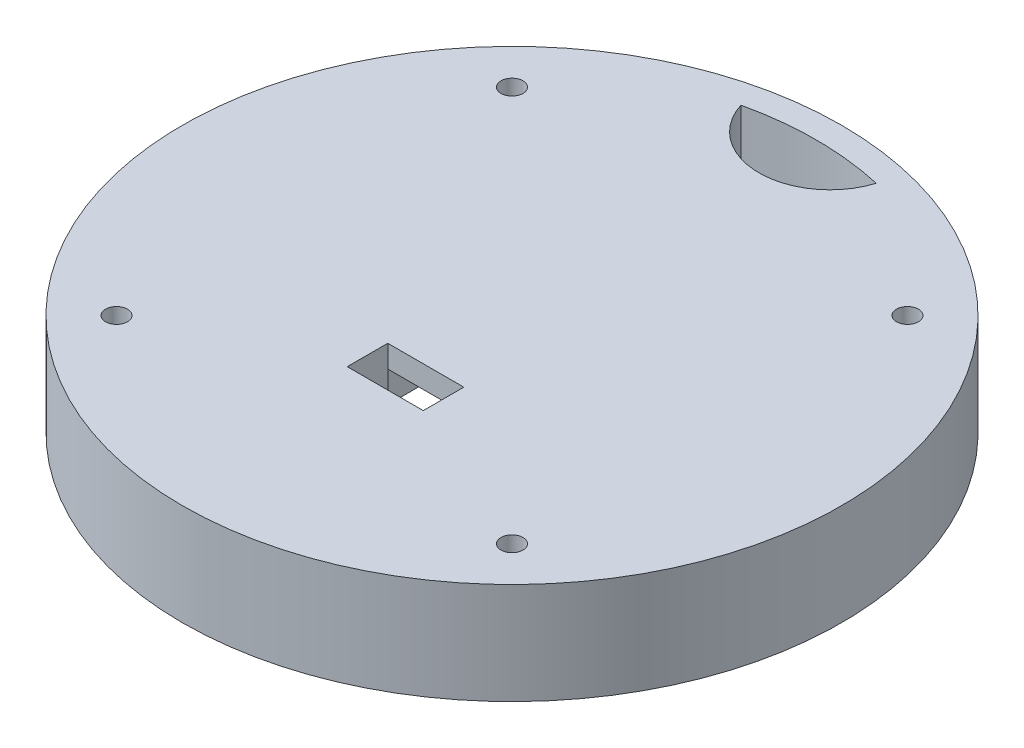
SolidWorks part; units mm, degrees
ref_plane "Front Plane" through (0, 0, 0) normal (0, 0, 1) x (1, 0, 0)
ref_plane "Top Plane" through (0, 0, 0) normal (0, 1, 0) x (1, 0, 0)
ref_plane "Right Plane" through (0, 0, 0) normal (1, 0, 0) x (0, 0, -1)
sketch "Sketch1" plane through (0, 0, 0) normal (0, 1, 0) x (1, 0, 0)
  line L1 (57.15, 57.15) -> (-57.15, 57.15) construction
  line L2 (57.15, 57.15) -> (57.15, -57.15) construction
  line L3 (57.15, -57.15) -> (-57.15, -57.15) construction
  line L4 (-57.15, 57.15) -> (-57.15, -57.15) construction
  line L5 (57.15, 57.15) -> (-57.15, -57.15) construction
  line L6 (57.15, -57.15) -> (-57.15, 57.15) construction
  line L7 (21.59, 21.59) -> (-21.59, 21.59)
  line L8 (21.59, 21.59) -> (21.59, -21.59)
  line L9 (21.59, -21.59) -> (-21.59, -21.59)
  line L10 (-21.59, 21.59) -> (-21.59, -21.59)
  line L11 (21.59, 21.59) -> (-21.59, -21.59) construction
  line L12 (21.59, -21.59) -> (-21.59, 21.59) construction
  circle A0 centre (-49.53, 49.53) radius 2.75
  circle A1 centre (49.53, 49.53) radius 2.75
  circle A2 centre (49.53, -49.53) radius 2.75
  circle A3 centre (-49.53, -49.53) radius 2.75
  circle A4 centre (0, 0) radius 82.55
  arc A6 (-16.9561, 74.2895) -> (16.9561, 74.2895) centre (0, 79.6392) ccw
  circle A7 centre (0, 0) radius 76.2
  point P0 (0, 0)
  point P14 (0, 0)
  point P25 (0, 0)
  dimension "D4" = 5.5
  dimension "D6" = 165.1
  dimension "D7" = 17.78
  dimension "D10" = 152.4
  dimension "D1" = 99.06
  dimension "D2" = 99.06
  dimension "D3" = 114.3
  dimension "D5" = 43.18
  dimension "D8" = 25.714
extrude "Boss-Extrude3" add sketch "Sketch1" along normal blind 25.4 contours A7 | A4 A7 | A7 A3 A2 A1 A0 L10 L7 L8 L9 | L7 L10 L9 L8 | A0 | A1 | A2 | A3 region at (0, 0, 0) region at (-49.53, 0, -49.53) region at (49.53, 0, -49.53) region at (49.53, 0, 49.53) region at (-49.53, 0, 49.53) region at (-80.2151, 0, 0) region at (0, 0, -69.8575) region at (0, 0, -59.7174)
extrude "Cut-Extrude1" cut sketch "Sketch1<6>" along normal blind 2540 contours A7 region at (0, 0, -69.8575)
sketch "Sketch1<6>" plane through (0, 0, 0) normal (0, 1, 0) x (1, 0, 0) same geometry as "Sketch1"
extrude "Cut-Extrude2" cut sketch "Sketch1<7>" along normal blind 19.812 contours L7 L10 L9 L8 region at (0, 0, 0)
sketch "Sketch1<7>" plane through (0, 0, 0) normal (0, 1, 0) x (1, 0, 0) same geometry as "Sketch1"
sketch "Sketch3" plane through (0, 0, 0) normal (0, -1, 0) x (1, 0, 0)
  line L0 (21.59, 21.59) -> (-21.59, 21.59) construction
  line L1 (-9.525, 21.59) -> (9.525, 21.59)
  line L2 (-9.525, 21.59) -> (-9.525, 31.75)
  line L3 (-9.525, 31.75) -> (9.525, 31.75)
  line L4 (9.525, 21.59) -> (9.525, 31.75)
  line L5 (0, 31.75) -> (0, 0) construction
  point P9 (0, 0)
  dimension "D1" = 19.05
  dimension "D2" = 10.16
extrude "Cut-Extrude3" cut sketch "Sketch3" against normal through all
extrude "Cut-Extrude4" cut sketch "Sketch1<8>" along normal blind 6 contours A3 | A2 | A0 | A1 region at (-49.53, 0, -49.53) region at (49.53, 0, -49.53) region at (49.53, 0, 49.53) region at (-49.53, 0, 49.53)
sketch "Sketch1<8>" plane through (0, 0, 0) normal (0, 1, 0) x (1, 0, 0) same geometry as "Sketch1"
extrude "Cut-Extrude5" cut sketch "Sketch1<10>" against normal blind 6 from offset 25.4 contours A0 | A1 | A3 | A2 region at (-49.53, 0, -49.53) region at (49.53, 0, -49.53) region at (49.53, 0, 49.53) region at (-49.53, 0, 49.53)
sketch "Sketch1<10>" plane through (0, 0, 0) normal (0, 1, 0) x (1, 0, 0) same geometry as "Sketch1"
